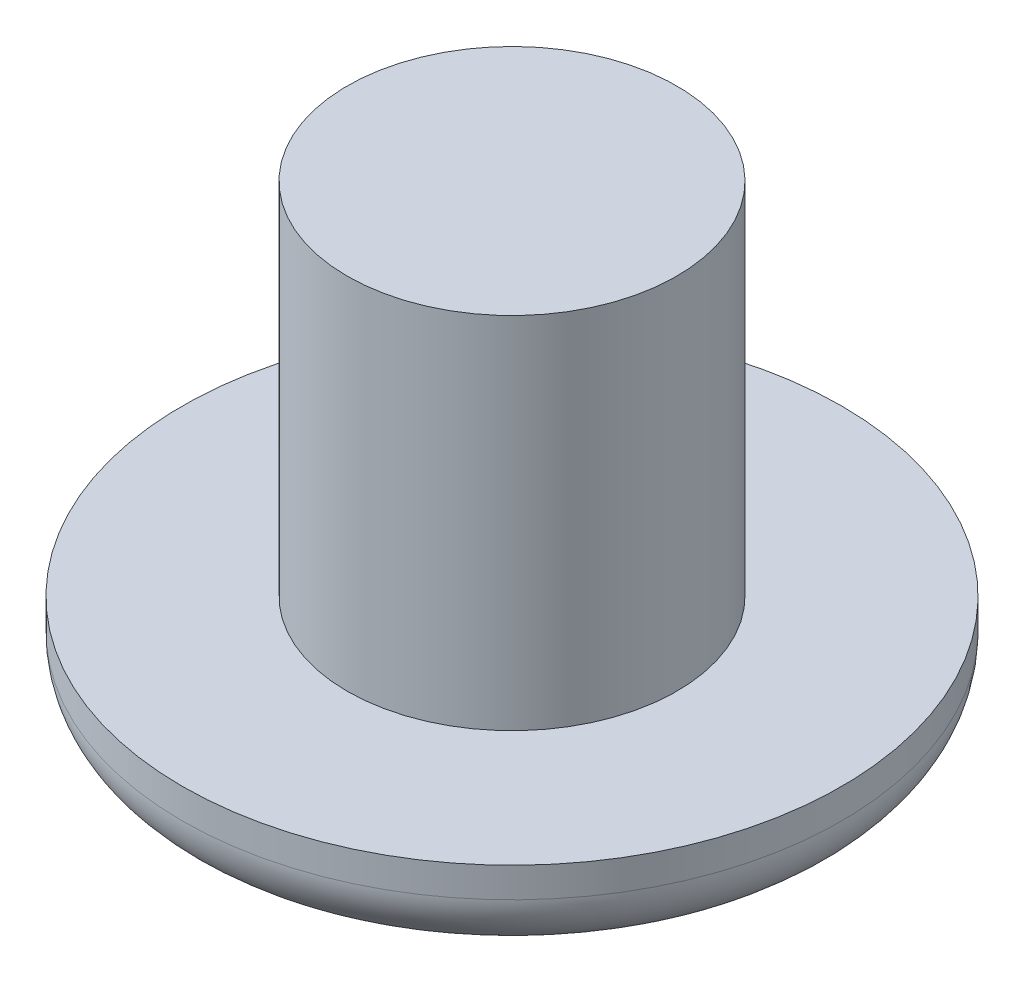
SolidWorks part; units mm, degrees
ref_plane "Front Plane" through (0, 0, 0) normal (0, 0, 1) x (1, 0, 0)
ref_plane "Top Plane" through (0, 0, 0) normal (0, 1, 0) x (1, 0, 0)
ref_plane "Right Plane" through (0, 0, 0) normal (1, 0, 0) x (0, 0, -1)
sketch "Sketch1" plane through (0, 0, 0) normal (0, 1, 0) x (1, 0, 0)
  line L0 (0, 0) -> (0, 23673.9858) construction
  line L1 (0, 0) -> (23673.9858, 0) construction
  circle A0 centre (0, 0) radius 11
  circle A1 centre (0, 0) radius 5.5
  dimension "D1" = 22
  dimension "D2" = 11
extrude "Boss-Extrude1" add sketch "Sketch1" along normal blind 3
extrude "Boss-Extrude2" add sketch "Sketch1<2>" along normal blind 15 contours A1 region at (0, 0, 0)
sketch "Sketch1<2>" plane through (0, 0, 0) normal (0, 1, 0) x (1, 0, 0) same geometry as "Sketch1"
fillet "Fillet1" radius 2 1 edges at (0, 0, 11)
